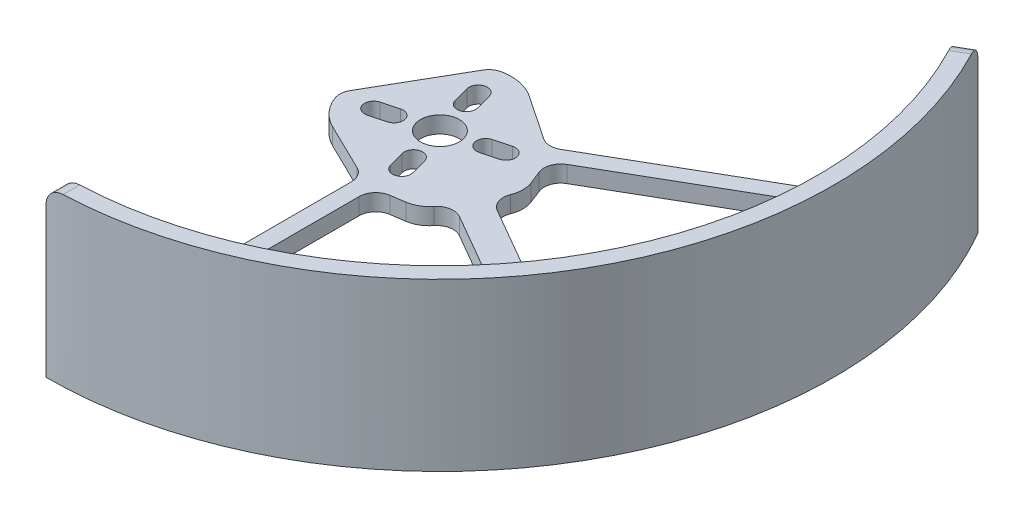
SolidWorks part; units mm, degrees
material "ABS"
ref_plane "Front Plane" through (0, 0, 0) normal (0, 0, 1) x (1, 0, 0)
ref_plane "Top Plane" through (0, 0, 0) normal (0, 1, 0) x (1, 0, 0)
ref_plane "Right Plane" through (0, 0, 0) normal (1, 0, 0) x (0, 0, -1)
sketch "Sketch1" plane through (0, 0, 0) normal (0, 1, 0) x (1, 0, 0)
  line L0 (0, 0) -> (0, -71) construction
  line L1 (0, 0) -> (61.4878, 35.5) construction
  line L2 (0, -68) -> (0, -71)
  line L3 (58.8897, 34) -> (61.4878, 35.5)
  arc A0 (0, -68) -> (58.8897, 34) centre (0, 0) ccw
  arc A1 (0, -71) -> (61.4878, 35.5) centre (0, 0) ccw
  dimension "D1" = 136
  dimension "D2" = 142
  dimension "D3" = 120
extrude "Boss-Extrude1" add sketch "Sketch1" along normal blind 30
sketch "Sketch4" plane through (0, 0, 0) normal (0, -1, 0) x (1, 0, 0)
  line L0 (2.673, -13.4439) -> (12.8584, -6.5738) construction
  line L1 (14.7145, -4.2611) -> (16.3536, -0.1001) construction
  line L3 (8.0901, 14.2127) -> (3.667, 14.8737) construction
  line L5 (2.673, -13.4439) -> (12.1794, -7.0318)
  line L6 (14.7145, -4.2611) -> (16.3536, -0.1001)
  line L7 (11.6812, 11.7676) -> (16.0316, 4.2324) construction
  line L8 (8.0901, 14.2127) -> (3.667, 14.8737)
  line L9 (0, 14.0636) -> (-10.3063, 9.0369)
  line L10 (58.8897, -34) -> (12.1794, -7.0318)
  line L11 (61.4878, -35.5) -> (58.8897, -34) construction
  line L12 (60.3324, -31.3688) -> (14.4281, -4.866)
  line L13 (16.0316, 4.2324) -> (60.9443, 30.1628) construction
  line L14 (11.6812, 11.7676) -> (56.5939, 37.6979) construction
  line L15 (0, 68) -> (0, 14.0636)
  line L16 (3, 14.9281) -> (3, 67.9338)
  line L17 (60.0193, 31.7649) -> (57.5193, 36.095) construction
  line L18 (61.4878, 35.5) -> (57.7678, 33.3523) construction
  line L19 (9.4178, -2.5235) -> (6.52, -1.747) construction
  line L20 (8.9907, -4.1173) -> (6.0929, -3.3408)
  line L21 (9.8448, -0.9297) -> (6.9471, -0.1533)
  line L22 (2.5235, 9.4178) -> (1.747, 6.52) construction
  line L23 (4.1173, 8.9907) -> (3.3408, 6.0929)
  line L24 (0.9297, 9.8448) -> (0.1533, 6.9471)
  line L25 (-6.52, 1.747) -> (-9.4178, 2.5235) construction
  line L26 (-6.9471, 0.1533) -> (-9.8448, 0.9297)
  line L27 (-6.0929, 3.3408) -> (-8.9907, 4.1173)
  line L28 (-2.5235, -9.4178) -> (-1.747, -6.52) construction
  line L29 (-4.1173, -8.9907) -> (-3.3408, -6.0929)
  line L30 (-0.9297, -9.8448) -> (-0.1533, -6.9471)
  line L31 (-4.988, -14.3843) -> (-14.9511, 2.8724)
  line L32 (12.6066, 10.1647) -> (57.6001, 36.1417)
  line L33 (15.1066, 5.8346) -> (60.1001, 31.8116)
  line L34 (16.0316, 4.2324) -> (15.1066, 5.8346)
  line L35 (11.6812, 11.7676) -> (12.6066, 10.1647)
  arc A0 (-4.988, -14.3843) -> (2.673, -13.4439) centre (-2.0801, -6.3971) ccw construction
  arc A1 (12.8584, -6.5738) -> (14.7145, -4.2611) centre (10.0624, -2.4286) ccw construction
  arc A2 (16.3536, -0.1001) -> (16.0316, 4.2324) centre (11.7015, 1.7324) ccw construction
  arc A3 (11.6812, 11.7676) -> (8.0901, 14.2127) centre (7.3511, 9.2676) ccw construction
  arc A5 (-10.3063, 9.0369) -> (-14.9511, 2.8724) centre (-6.5801, 1.3971) ccw construction
  arc A6 (-4.988, -14.3843) -> (2.673, -13.4439) centre (-2.0801, -6.3971) ccw
  arc A7 (14.4281, -4.866) -> (14.7145, -4.2611) centre (10.0624, -2.4286) ccw
  arc A8 (16.3536, -0.1001) -> (16.0316, 4.2324) centre (11.7015, 1.7324) ccw
  arc A9 (11.6812, 11.7676) -> (8.0901, 14.2127) centre (7.3511, 9.2676) ccw
  arc A10 (3.667, 14.8737) -> (3, 14.9281) centre (2.928, 9.9286) ccw
  arc A11 (-10.3063, 9.0369) -> (-14.9511, 2.8724) centre (-6.5801, 1.3971) ccw
  arc A12 (61.4878, -35.5) -> (0, 71) centre (0, 0) ccw construction
  arc A14 (58.8897, -34) -> (60.3324, -31.3688) centre (0, 0) ccw
  arc A15 (8.9907, -4.1173) -> (9.8448, -0.9297) centre (9.4178, -2.5235) ccw
  arc A16 (6.9471, -0.1533) -> (6.0929, -3.3408) centre (6.52, -1.747) ccw
  arc A17 (4.1173, 8.9907) -> (0.9297, 9.8448) centre (2.5235, 9.4178) ccw
  arc A18 (0.1533, 6.9471) -> (3.3408, 6.0929) centre (1.747, 6.52) ccw
  arc A19 (-6.9471, 0.1533) -> (-6.0929, 3.3408) centre (-6.52, 1.747) ccw
  arc A20 (-8.9907, 4.1173) -> (-9.8448, 0.9297) centre (-9.4178, 2.5235) ccw
  arc A21 (-4.1173, -8.9907) -> (-0.9297, -9.8448) centre (-2.5235, -9.4178) ccw
  arc A22 (-0.1533, -6.9471) -> (-3.3408, -6.0929) centre (-1.747, -6.52) ccw
  circle A23 centre (0, 0) radius 3.5
  arc A24 (60.1001, 31.8116) -> (57.6001, 36.1417) centre (0, 0) ccw
  arc A25 (3, 67.9338) -> (0, 68) centre (0, 0) ccw
  arc A26 (58.8897, -34) -> (0, 68) centre (0, 0) ccw construction
  point P46 (7.9689, -2.1353)
  point P51 (2.1353, 7.9689)
  point P60 (-7.9689, 2.1353)
  point P69 (-2.1353, -7.9689)
  dimension "D3" = 1.65
  dimension "D4" = 7
  dimension "D5" = 5
  dimension "D1" = 3
  dimension "D2" = 3
  dimension "D6" = 1.85
extrude "Boss-Extrude2" add sketch "Sketch4" against normal blind 3
fillet "Fillet3" radius 3 14 edges at (0, 30, 69.5) (60.1888, 30, -34.75) (60.3324, 1.5, -31.3688) (14.4281, 1.5, -4.866) (15.1066, 1.5, 5.8346) (60.1001, 1.5, 31.8116) (57.6001, 1.5, 36.1417) (12.6066, 1.5, 10.1647) (3, 1.5, 14.9281) (3, 1.5, 67.9338) (0, 1.5, 14.0636) (-14.9511, 1.5, 2.8724) (-4.988, 1.5, -14.3843) (12.1794, 1.5, -7.0318)
chamfer "Chamfer1" distance 2 angle 45 3 edges at (60.3977, 3, -31.2428) (3.1418, 3, 67.9274) (58.89, 3, 33.9996)
